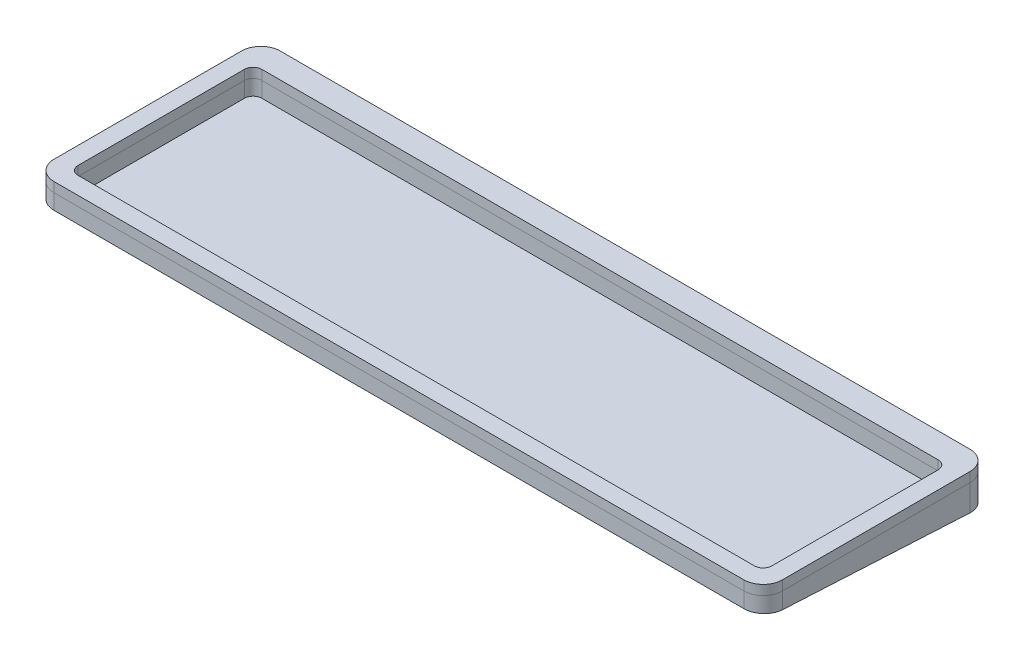
SolidWorks part; units mm, degrees
ref_plane "Front Plane" through (0, 0, 0) normal (0, 0, 1) x (1, 0, 0)
ref_plane "Top Plane" through (0, 0, 0) normal (0, 1, 0) x (1, 0, 0)
ref_plane "Right Plane" through (0, 0, 0) normal (1, 0, 0) x (0, 0, -1)
sketch "Sketch1" plane through (0, 0, 0) normal (0, 1, 0) x (1, 0, 0)
  line L0 (-179.825, 47.6224) -> (-179.825, 47.625)
  line L1 (-179.8217, 47.625) -> (179.825, 47.625)
  line L2 (-179.825, 47.6224) -> (-179.825, -47.625)
  line L3 (-179.825, -47.625) -> (179.825, -47.625)
  line L4 (179.825, 47.625) -> (179.825, -47.625)
  line L5 (-179.825, 47.625) -> (179.825, -47.625) construction
  line L6 (-179.825, -47.625) -> (179.825, 47.625) construction
  line L7 (-179.825, 47.625) -> (-179.8217, 47.625)
  circle A4 centre (157.075, 19.175) radius 1.1
  circle A5 centre (136.925, -16.775) radius 1.1
  circle A6 centre (-153.475, 33.725) radius 1.1
  circle A7 centre (17.925, 22.275) radius 1.1
  circle A8 centre (17.875, -35.075) radius 1.1
  circle A9 centre (-130.375, -35.725) radius 1.1
  point P0 (0, 0)
  point P7 (179.7842, -47.6142)
  point P8 (179.825, -47.6777)
  point P9 (179.825, 47.6224)
  point P11 (0, 0)
  point P12 (-179.8245, -47.6227)
  point P13 (179.8032, 47.6192)
  point P14 (-179.825, -47.6082)
  point P17 (-179.8242, 47.6248)
  point P30 (-179.7778, 47.6125)
  point P31 (-179.8245, 47.625)
  dimension "D4" = 2.2
  dimension "D7" = 2.2
  dimension "D8" = 2.2
  dimension "D9" = 2.2
  dimension "D10" = 2.2
  dimension "D11" = 2.2
  dimension "D1" = 359.65
  dimension "D2" = 95.25
  dimension "D5" = 22.75
  dimension "D6" = 28.45
  dimension "D12" = 42.9
  dimension "D13" = 30.85
  dimension "D14" = 25.35
  dimension "D15" = 161.9
  dimension "D16" = 12.55
  dimension "D17" = 161.95
  dimension "D18" = 11.9
  dimension "D19" = 49.45
  dimension "D20" = 13.9
  dimension "D21" = 26.35
sketch "Sketch2" plane through (0, 0, 0) normal (0, 1, 0) x (1, 0, 0)
  line L0 (-188.825, 54.625) -> (-188.825, 60.625)
  line L1 (-188.825, 60.625) -> (-182.825, 60.625)
  line L4 (-179.825, 46.625) -> (-179.825, -46.625)
  line L5 (-178.825, -47.625) -> (178.825, -47.625)
  line L6 (179.825, 46.625) -> (179.825, -46.625)
  line L7 (-178.825, 47.625) -> (178.825, 47.625)
  line L8 (-179.825, 46.625) -> (-179.825, 47.625)
  line L9 (-182.825, 60.625) -> (188.825, 60.625)
  line L10 (-188.825, 54.625) -> (-188.825, -56.625)
  line L11 (-188.825, -56.625) -> (188.825, -56.625)
  line L12 (188.825, 60.625) -> (188.825, -56.625)
  line L13 (-179.825, 47.625) -> (-178.825, 47.625)
  line L14 (-179.825, -46.625) -> (-179.825, -47.625)
  line L15 (-179.825, -47.625) -> (-178.825, -47.625)
  line L16 (178.825, -47.625) -> (179.825, -47.625)
  line L17 (179.825, -47.625) -> (179.825, -46.625)
  line L18 (178.825, 47.625) -> (179.825, 47.625)
  line L19 (179.825, 47.625) -> (179.825, 46.625)
  circle A0 centre (157.075, 19.175) radius 1.1 construction
  circle A1 centre (136.925, -16.775) radius 1.1 construction
  circle A2 centre (17.875, -35.075) radius 1.1 construction
  circle A3 centre (17.925, 22.275) radius 1.1 construction
  circle A4 centre (-153.475, 33.725) radius 1.1 construction
  circle A5 centre (-130.375, -35.725) radius 1.1 construction
  circle A10 centre (157.075, 19.175) radius 1.1
  circle A11 centre (136.925, -16.775) radius 1.1
  circle A12 centre (17.875, -35.075) radius 1.1
  circle A13 centre (17.925, 22.275) radius 1.1
  circle A14 centre (-153.475, 33.725) radius 1.1
  circle A15 centre (-130.375, -35.725) radius 1.1
  point P14 (188.825, 60.625)
  point P29 (188.825, 60.2138)
  point P30 (0, 0)
  point P32 (188.825, -56.625)
  point P33 (188.825, -56.1865)
  point P34 (-188.825, -56.625)
  point P37 (0, 0)
  dimension "D1" = 13
  dimension "D2" = 9
  dimension "D3" = 9
  dimension "D4" = 9
extrude "Boss-Extrude1" add sketch "Sketch2" along normal blind 13 contours L10 L11 L12 L9 L18 L19 L6 L17 L16 L5 L15 L14 L4 L8 L13 L7 region at (-184.8707, 0, -57.625)
sketch "Sketch4" plane through (0, 0, 0) normal (0, -1, 0) x (1, 0, 0)
  line L0 (188.825, -60.625) -> (188.825, 56.625) construction
  line L1 (-188.825, -60.625) -> (188.825, -60.625) construction
  line L2 (-188.825, -60.625) -> (-188.825, 56.625) construction
  line L3 (-188.825, 56.625) -> (188.825, 56.625) construction
  line L4 (-179.825, 47.625) -> (-179.825, -47.625)
  line L5 (179.825, 47.625) -> (-179.825, 47.625)
  line L6 (179.825, -47.625) -> (179.825, 47.625)
  line L7 (-179.825, -47.625) -> (179.825, -47.625)
  line L8 (-179.825, 47.625) -> (-179.825, -47.625)
  line L10 (179.825, -47.625) -> (179.825, 47.625)
  line L11 (-179.825, -47.625) -> (179.825, -47.625)
  line L12 (188.825, -60.625) -> (188.825, 56.625)
  line L13 (-188.825, -60.625) -> (188.825, -60.625)
  line L14 (-188.825, -60.625) -> (-188.825, 56.625)
  line L15 (-188.825, 56.625) -> (188.825, 56.625)
  line M10 (-179.825, -47.625) -> (-179.825, 47.625)
  line M12 (-179.825, 47.625) -> (179.825, 47.625)
  line M14 (179.825, 47.625) -> (179.825, -47.625)
  line M16 (179.825, -47.625) -> (-179.825, -47.625)
  line M17 (-188.825, 56.625) -> (-188.825, -60.625)
  line M19 (-188.825, -60.625) -> (188.825, -60.625)
  line M21 (188.825, -60.625) -> (188.825, 56.625)
  line M23 (188.825, 56.625) -> (-188.825, 56.625)
  dimension "D1" = 0
extrude "Boss-Extrude3" add sketch "Sketch4" along normal blind 10.5 contours M17 M19 M21 M23 M16 M10 M12 M14 | M16 M14 M12 M10 region at (0, 0, 0) region at (0, 0, -56.6707)
sketch "Sketch8" plane through (-188.825, 0, 0) normal (-1, 0, 0) x (0, 0, 1)
  line L0 (54.6255, 0) -> (-57.625, 0) construction
  line L1 (-60.625, 13) -> (-60.625, -10.5) construction
  line L4 (-60.625, -6.1008) -> (-60.625, -10.5)
  line L5 (-60.625, -10.5) -> (56.625, -10.5)
  line L11 (56.625, 0.044) -> (56.625, -10.5)
  line L13 (-60.625, -6.1008) -> (56.625, 0.044)
  point P3 (-60.625, -6.1008)
  dimension "D1" = 2
  dimension "D2" = 10.5
extrude "Cut-Extrude4" cut sketch "Sketch8" against normal blind 400
sketch "Sketch9" plane through (0, 0, 0) normal (0, 1, 0) x (1, 0, 0)
  line L0 (-121.9453, 45.1) -> (-108.9453, 45.1)
  line L1 (-121.9453, 31.1) -> (-108.9453, 31.1)
  line L2 (-122.4453, 44.6) -> (-122.4453, 31.6)
  line L3 (-108.4453, 44.6) -> (-108.4453, 31.6)
  line L4 (-102.8953, 45.1) -> (-89.8953, 45.1)
  line L5 (-102.8953, 31.1) -> (-89.8953, 31.1)
  line L6 (-103.3953, 44.6) -> (-103.3953, 31.6)
  line L7 (-89.3953, 44.6) -> (-89.3953, 31.6)
  line L8 (-83.8453, 45.1) -> (-70.8453, 45.1)
  line L9 (-83.8453, 31.1) -> (-70.8453, 31.1)
  line L10 (-84.3453, 44.6) -> (-84.3453, 31.6)
  line L11 (-70.3453, 44.6) -> (-70.3453, 31.6)
  line L12 (-64.7953, 45.1) -> (-51.7953, 45.1)
  line L13 (-64.7953, 31.1) -> (-51.7953, 31.1)
  line L14 (-65.2953, 44.6) -> (-65.2953, 31.6)
  line L15 (-51.2953, 44.6) -> (-51.2953, 31.6)
  line L16 (-45.7453, 45.1) -> (-32.7453, 45.1)
  line L17 (-45.7453, 31.1) -> (-32.7453, 31.1)
  line L18 (-46.2453, 44.6) -> (-46.2453, 31.6)
  line L19 (-32.2453, 44.6) -> (-32.2453, 31.6)
  line L20 (-26.6953, 45.1) -> (-13.6953, 45.1)
  line L21 (-26.6953, 31.1) -> (-13.6953, 31.1)
  line L22 (-27.1953, 44.6) -> (-27.1953, 31.6)
  line L23 (-13.1953, 44.6) -> (-13.1953, 31.6)
  line L24 (-7.6453, 45.1) -> (5.3547, 45.1)
  line L25 (-7.6453, 31.1) -> (5.3547, 31.1)
  line L26 (-8.1453, 44.6) -> (-8.1453, 31.6)
  line L27 (5.8547, 44.6) -> (5.8547, 31.6)
  line L28 (11.4047, 45.1) -> (24.4047, 45.1)
  line L29 (11.4047, 31.1) -> (24.4047, 31.1)
  line L30 (10.9047, 44.6) -> (10.9047, 31.6)
  line L31 (24.9047, 44.6) -> (24.9047, 31.6)
  line L32 (30.4547, 45.1) -> (43.4547, 45.1)
  line L33 (30.4547, 31.1) -> (43.4547, 31.1)
  line L34 (29.9547, 44.6) -> (29.9547, 31.6)
  line L35 (43.9547, 44.6) -> (43.9547, 31.6)
  line L36 (49.5047, 45.1) -> (62.5047, 45.1)
  line L37 (49.5047, 31.1) -> (62.5047, 31.1)
  line L38 (49.0047, 44.6) -> (49.0047, 31.6)
  line L39 (63.0047, 44.6) -> (63.0047, 31.6)
  line L40 (68.5547, 45.1) -> (81.5547, 45.1)
  line L41 (68.5547, 31.1) -> (81.5547, 31.1)
  line L42 (68.0547, 44.6) -> (68.0547, 31.6)
  line L43 (82.0547, 44.6) -> (82.0547, 31.6)
  line L44 (87.6047, 45.1) -> (100.6047, 45.1)
  line L45 (87.6047, 31.1) -> (100.6047, 31.1)
  line L46 (87.1047, 44.6) -> (87.1047, 31.6)
  line L47 (101.1047, 44.6) -> (101.1047, 31.6)
  line L48 (106.6547, 45.1) -> (119.6547, 45.1)
  line L49 (106.6547, 31.1) -> (119.6547, 31.1)
  line L50 (106.1547, 44.6) -> (106.1547, 31.6)
  line L51 (120.1547, 44.6) -> (120.1547, 31.6)
  line L52 (135.2297, 45.1) -> (148.2297, 45.1)
  line L53 (135.2297, 31.1) -> (148.2297, 31.1)
  line L54 (134.7297, 44.6) -> (134.7297, 31.6)
  line L55 (148.7297, 44.6) -> (148.7297, 31.6)
  line L56 (150.6677, 44.1) -> (156.6677, 44.1)
  line L57 (150.6677, 29.1) -> (156.6677, 29.1)
  line L58 (150.1677, 43.6) -> (150.1677, 29.6)
  line L59 (157.1677, 43.6) -> (157.1677, 29.6)
  line L60 (126.7917, 44.1) -> (132.7917, 44.1)
  line L61 (126.7917, 29.1) -> (132.7917, 29.1)
  line L62 (126.2917, 43.6) -> (126.2917, 29.6)
  line L63 (133.2917, 43.6) -> (133.2917, 29.6)
  line L64 (163.8047, 45.1) -> (176.8047, 45.1)
  line L65 (163.8047, 31.1) -> (176.8047, 31.1)
  line L66 (163.3047, 44.6) -> (163.3047, 31.6)
  line L67 (177.3047, 44.6) -> (177.3047, 31.6)
  line L68 (-117.1828, 26.05) -> (-104.1828, 26.05)
  line L69 (-117.1828, 12.05) -> (-104.1828, 12.05)
  line L70 (-117.6828, 25.55) -> (-117.6828, 12.55)
  line L71 (-103.6828, 25.55) -> (-103.6828, 12.55)
  line L72 (-93.3703, 26.05) -> (-80.3703, 26.05)
  line L73 (-93.3703, 12.05) -> (-80.3703, 12.05)
  line L74 (-93.8703, 25.55) -> (-93.8703, 12.55)
  line L75 (-79.8703, 25.55) -> (-79.8703, 12.55)
  line L76 (-74.3203, 26.05) -> (-61.3203, 26.05)
  line L77 (-74.3203, 12.05) -> (-61.3203, 12.05)
  line L78 (-74.8203, 25.55) -> (-74.8203, 12.55)
  line L79 (-60.8203, 25.55) -> (-60.8203, 12.55)
  line L80 (-55.2703, 26.05) -> (-42.2703, 26.05)
  line L81 (-55.2703, 12.05) -> (-42.2703, 12.05)
  line L82 (-55.7703, 25.55) -> (-55.7703, 12.55)
  line L83 (-41.7703, 25.55) -> (-41.7703, 12.55)
  line L84 (-36.2203, 26.05) -> (-23.2203, 26.05)
  line L85 (-36.2203, 12.05) -> (-23.2203, 12.05)
  line L86 (-36.7203, 25.55) -> (-36.7203, 12.55)
  line L87 (-22.7203, 25.55) -> (-22.7203, 12.55)
  line L88 (-17.1703, 26.05) -> (-4.1703, 26.05)
  line L89 (-17.1703, 12.05) -> (-4.1703, 12.05)
  line L90 (-17.6703, 25.55) -> (-17.6703, 12.55)
  line L91 (-3.6703, 25.55) -> (-3.6703, 12.55)
  line L92 (1.8797, 26.05) -> (14.8797, 26.05)
  line L93 (1.8797, 12.05) -> (14.8797, 12.05)
  line L94 (1.3797, 25.55) -> (1.3797, 12.55)
  line L95 (15.3797, 25.55) -> (15.3797, 12.55)
  line L96 (20.9297, 26.05) -> (33.9297, 26.05)
  line L97 (20.9297, 12.05) -> (33.9297, 12.05)
  line L98 (20.4297, 25.55) -> (20.4297, 12.55)
  line L99 (34.4297, 25.55) -> (34.4297, 12.55)
  line L100 (39.9797, 26.05) -> (52.9797, 26.05)
  line L101 (39.9797, 12.05) -> (52.9797, 12.05)
  line L102 (39.4797, 25.55) -> (39.4797, 12.55)
  line L103 (53.4797, 25.55) -> (53.4797, 12.55)
  line L104 (59.0297, 26.05) -> (72.0297, 26.05)
  line L105 (59.0297, 12.05) -> (72.0297, 12.05)
  line L106 (58.5297, 25.55) -> (58.5297, 12.55)
  line L107 (72.5297, 25.55) -> (72.5297, 12.55)
  line L108 (78.0797, 26.05) -> (91.0797, 26.05)
  line L109 (78.0797, 12.05) -> (91.0797, 12.05)
  line L110 (77.5797, 25.55) -> (77.5797, 12.55)
  line L111 (91.5797, 25.55) -> (91.5797, 12.55)
  line L112 (97.1297, 26.05) -> (110.1297, 26.05)
  line L113 (97.1297, 12.05) -> (110.1297, 12.05)
  line L114 (96.6297, 25.55) -> (96.6297, 12.55)
  line L115 (110.6297, 25.55) -> (110.6297, 12.55)
  line L116 (116.1797, 26.05) -> (129.1797, 26.05)
  line L117 (116.1797, 12.05) -> (129.1797, 12.05)
  line L118 (115.6797, 25.55) -> (115.6797, 12.55)
  line L119 (129.6797, 25.55) -> (129.6797, 12.55)
  line L120 (139.9922, 26.05) -> (152.9922, 26.05)
  line L121 (139.9922, 12.05) -> (152.9922, 12.05)
  line L122 (139.4922, 25.55) -> (139.4922, 12.55)
  line L123 (153.4922, 25.55) -> (153.4922, 12.55)
  line L124 (163.8047, 26.05) -> (176.8047, 26.05)
  line L125 (163.8047, 12.05) -> (176.8047, 12.05)
  line L126 (163.3047, 25.55) -> (163.3047, 12.55)
  line L127 (177.3047, 25.55) -> (177.3047, 12.55)
  line L128 (-114.8016, 7) -> (-101.8016, 7)
  line L129 (-114.8016, -7) -> (-101.8016, -7)
  line L130 (-115.3016, 6.5) -> (-115.3016, -6.5)
  line L131 (-101.3016, 6.5) -> (-101.3016, -6.5)
  line L132 (-88.6078, 7) -> (-75.6078, 7)
  line L133 (-88.6078, -7) -> (-75.6078, -7)
  line L134 (-89.1078, 6.5) -> (-89.1078, -6.5)
  line L135 (-75.1078, 6.5) -> (-75.1078, -6.5)
  line L136 (-69.5578, 7) -> (-56.5578, 7)
  line L137 (-69.5578, -7) -> (-56.5578, -7)
  line L138 (-70.0578, 6.5) -> (-70.0578, -6.5)
  line L139 (-56.0578, 6.5) -> (-56.0578, -6.5)
  line L140 (-50.5078, 7) -> (-37.5078, 7)
  line L141 (-50.5078, -7) -> (-37.5078, -7)
  line L142 (-51.0078, 6.5) -> (-51.0078, -6.5)
  line L143 (-37.0078, 6.5) -> (-37.0078, -6.5)
  line L144 (-31.4578, 7) -> (-18.4578, 7)
  line L145 (-31.4578, -7) -> (-18.4578, -7)
  line L146 (-31.9578, 6.5) -> (-31.9578, -6.5)
  line L147 (-17.9578, 6.5) -> (-17.9578, -6.5)
  line L148 (-12.4078, 7) -> (0.5922, 7)
  line L149 (-12.4078, -7) -> (0.5922, -7)
  line L150 (-12.9078, 6.5) -> (-12.9078, -6.5)
  line L151 (1.0922, 6.5) -> (1.0922, -6.5)
  line L152 (6.6422, 7) -> (19.6422, 7)
  line L153 (6.6422, -7) -> (19.6422, -7)
  line L154 (6.1422, 6.5) -> (6.1422, -6.5)
  line L155 (20.1422, 6.5) -> (20.1422, -6.5)
  line L156 (25.6922, 7) -> (38.6922, 7)
  line L157 (25.6922, -7) -> (38.6922, -7)
  line L158 (25.1922, 6.5) -> (25.1922, -6.5)
  line L159 (39.1922, 6.5) -> (39.1922, -6.5)
  line L160 (44.7422, 7) -> (57.7422, 7)
  line L161 (44.7422, -7) -> (57.7422, -7)
  line L162 (44.2422, 6.5) -> (44.2422, -6.5)
  line L163 (58.2422, 6.5) -> (58.2422, -6.5)
  line L164 (63.7922, 7) -> (76.7922, 7)
  line L165 (63.7922, -7) -> (76.7922, -7)
  line L166 (63.2922, 6.5) -> (63.2922, -6.5)
  line L167 (77.2922, 6.5) -> (77.2922, -6.5)
  line L168 (82.8422, 7) -> (95.8422, 7)
  line L169 (82.8422, -7) -> (95.8422, -7)
  line L170 (82.3422, 6.5) -> (82.3422, -6.5)
  line L171 (96.3422, 6.5) -> (96.3422, -6.5)
  line L172 (101.8922, 7) -> (114.8922, 7)
  line L173 (101.8922, -7) -> (114.8922, -7)
  line L174 (101.3922, 6.5) -> (101.3922, -6.5)
  line L175 (115.3922, 6.5) -> (115.3922, -6.5)
  line L176 (132.8484, 7) -> (145.8484, 7)
  line L177 (132.8484, -7) -> (145.8484, -7)
  line L178 (132.3484, 6.5) -> (132.3484, -6.5)
  line L179 (146.3484, 6.5) -> (146.3484, -6.5)
  line L180 (148.2864, 6) -> (154.2864, 6)
  line L181 (148.2864, -9) -> (154.2864, -9)
  line L182 (147.7864, 5.5) -> (147.7864, -8.5)
  line L183 (154.7864, 5.5) -> (154.7864, -8.5)
  line L184 (124.4104, 6) -> (130.4104, 6)
  line L185 (124.4104, -9) -> (130.4104, -9)
  line L186 (123.9104, 5.5) -> (123.9104, -8.5)
  line L187 (130.9104, 5.5) -> (130.9104, -8.5)
  line L188 (163.8047, 7) -> (176.8047, 7)
  line L189 (163.8047, -7) -> (176.8047, -7)
  line L190 (163.3047, 6.5) -> (163.3047, -6.5)
  line L191 (177.3047, 6.5) -> (177.3047, -6.5)
  line L192 (-110.0391, -12.05) -> (-97.0391, -12.05)
  line L193 (-110.0391, -26.05) -> (-97.0391, -26.05)
  line L194 (-110.5391, -12.55) -> (-110.5391, -25.55)
  line L195 (-96.5391, -12.55) -> (-96.5391, -25.55)
  line L196 (-94.6011, -13.05) -> (-88.6011, -13.05)
  line L197 (-94.6011, -28.05) -> (-88.6011, -28.05)
  line L198 (-95.1011, -13.55) -> (-95.1011, -27.55)
  line L199 (-88.1011, -13.55) -> (-88.1011, -27.55)
  line L200 (-118.4771, -13.05) -> (-112.4771, -13.05)
  line L201 (-118.4771, -28.05) -> (-112.4771, -28.05)
  line L202 (-118.9771, -13.55) -> (-118.9771, -27.55)
  line L203 (-111.9771, -13.55) -> (-111.9771, -27.55)
  line L204 (-79.0828, -12.05) -> (-66.0828, -12.05)
  line L205 (-79.0828, -26.05) -> (-66.0828, -26.05)
  line L206 (-79.5828, -12.55) -> (-79.5828, -25.55)
  line L207 (-65.5828, -12.55) -> (-65.5828, -25.55)
  line L208 (-60.0328, -12.05) -> (-47.0328, -12.05)
  line L209 (-60.0328, -26.05) -> (-47.0328, -26.05)
  line L210 (-60.5328, -12.55) -> (-60.5328, -25.55)
  line L211 (-46.5328, -12.55) -> (-46.5328, -25.55)
  line L212 (-40.9828, -12.05) -> (-27.9828, -12.05)
  line L213 (-40.9828, -26.05) -> (-27.9828, -26.05)
  line L214 (-41.4828, -12.55) -> (-41.4828, -25.55)
  line L215 (-27.4828, -12.55) -> (-27.4828, -25.55)
  line L216 (-21.9328, -12.05) -> (-8.9328, -12.05)
  line L217 (-21.9328, -26.05) -> (-8.9328, -26.05)
  line L218 (-22.4328, -12.55) -> (-22.4328, -25.55)
  line L219 (-8.4328, -12.55) -> (-8.4328, -25.55)
  line L220 (-2.8828, -12.05) -> (10.1172, -12.05)
  line L221 (-2.8828, -26.05) -> (10.1172, -26.05)
  line L222 (-3.3828, -12.55) -> (-3.3828, -25.55)
  line L223 (10.6172, -12.55) -> (10.6172, -25.55)
  line L224 (16.1672, -12.05) -> (29.1672, -12.05)
  line L225 (16.1672, -26.05) -> (29.1672, -26.05)
  line L226 (15.6672, -12.55) -> (15.6672, -25.55)
  line L227 (29.6672, -12.55) -> (29.6672, -25.55)
  line L228 (35.2172, -12.05) -> (48.2172, -12.05)
  line L229 (35.2172, -26.05) -> (48.2172, -26.05)
  line L230 (34.7172, -12.55) -> (34.7172, -25.55)
  line L231 (48.7172, -12.55) -> (48.7172, -25.55)
  line L232 (54.2672, -12.05) -> (67.2672, -12.05)
  line L233 (54.2672, -26.05) -> (67.2672, -26.05)
  line L234 (53.7672, -12.55) -> (53.7672, -25.55)
  line L235 (67.7672, -12.55) -> (67.7672, -25.55)
  line L236 (73.3172, -12.05) -> (86.3172, -12.05)
  line L237 (73.3172, -26.05) -> (86.3172, -26.05)
  line L238 (72.8172, -12.55) -> (72.8172, -25.55)
  line L239 (86.8172, -12.55) -> (86.8172, -25.55)
  line L240 (92.3672, -12.05) -> (105.3672, -12.05)
  line L241 (92.3672, -26.05) -> (105.3672, -26.05)
  line L242 (91.8672, -12.55) -> (91.8672, -25.55)
  line L243 (105.8672, -12.55) -> (105.8672, -25.55)
  line L244 (118.5609, -12.05) -> (131.5609, -12.05)
  line L245 (118.5609, -26.05) -> (131.5609, -26.05)
  line L246 (118.0609, -12.55) -> (118.0609, -25.55)
  line L247 (132.0609, -12.55) -> (132.0609, -25.55)
  line L248 (144.7547, -12.05) -> (157.7547, -12.05)
  line L249 (144.7547, -26.05) -> (157.7547, -26.05)
  line L250 (144.2547, -12.55) -> (144.2547, -25.55)
  line L251 (158.2547, -12.55) -> (158.2547, -25.55)
  line L252 (163.8047, -12.05) -> (176.8047, -12.05)
  line L253 (163.8047, -26.05) -> (176.8047, -26.05)
  line L254 (163.3047, -12.55) -> (163.3047, -25.55)
  line L255 (177.3047, -12.55) -> (177.3047, -25.55)
  line L256 (-119.5641, -31.1) -> (-106.5641, -31.1)
  line L257 (-119.5641, -45.1) -> (-106.5641, -45.1)
  line L258 (-120.0641, -31.6) -> (-120.0641, -44.6)
  line L259 (-106.0641, -31.6) -> (-106.0641, -44.6)
  line L260 (-95.7516, -31.1) -> (-82.7516, -31.1)
  line L261 (-95.7516, -45.1) -> (-82.7516, -45.1)
  line L262 (-96.2516, -31.6) -> (-96.2516, -44.6)
  line L263 (-82.2516, -31.6) -> (-82.2516, -44.6)
  line L264 (-71.9391, -31.1) -> (-58.9391, -31.1)
  line L265 (-71.9391, -45.1) -> (-58.9391, -45.1)
  line L266 (-72.4391, -31.6) -> (-72.4391, -44.6)
  line L267 (-58.4391, -31.6) -> (-58.4391, -44.6)
  line L268 (-0.5016, -31.1) -> (12.4984, -31.1)
  line L269 (-0.5016, -45.1) -> (12.4984, -45.1)
  line L270 (-1.0016, -31.6) -> (-1.0016, -44.6)
  line L271 (12.9984, -31.6) -> (12.9984, -44.6)
  line L272 (52.9984, -32.1) -> (58.9984, -32.1)
  line L273 (52.9984, -47.1) -> (58.9984, -47.1)
  line L274 (52.4984, -32.6) -> (52.4984, -46.6)
  line L275 (59.4984, -32.6) -> (59.4984, -46.6)
  line L276 (-47.0016, -32.1) -> (-41.0016, -32.1)
  line L277 (-47.0016, -47.1) -> (-41.0016, -47.1)
  line L278 (-47.5016, -32.6) -> (-47.5016, -46.6)
  line L279 (-40.5016, -32.6) -> (-40.5016, -46.6)
  line L280 (68.5547, -31.1) -> (81.5547, -31.1)
  line L281 (68.5547, -45.1) -> (81.5547, -45.1)
  line L282 (68.0547, -31.6) -> (68.0547, -44.6)
  line L283 (82.0547, -31.6) -> (82.0547, -44.6)
  line L284 (87.6047, -31.1) -> (100.6047, -31.1)
  line L285 (87.6047, -45.1) -> (100.6047, -45.1)
  line L286 (87.1047, -31.6) -> (87.1047, -44.6)
  line L287 (101.1047, -31.6) -> (101.1047, -44.6)
  line L288 (106.6547, -31.1) -> (119.6547, -31.1)
  line L289 (106.6547, -45.1) -> (119.6547, -45.1)
  line L290 (106.1547, -31.6) -> (106.1547, -44.6)
  line L291 (120.1547, -31.6) -> (120.1547, -44.6)
  line L292 (125.7047, -31.1) -> (138.7047, -31.1)
  line L293 (125.7047, -45.1) -> (138.7047, -45.1)
  line L294 (125.2047, -31.6) -> (125.2047, -44.6)
  line L295 (139.2047, -31.6) -> (139.2047, -44.6)
  line L296 (144.7547, -31.1) -> (157.7547, -31.1)
  line L297 (144.7547, -45.1) -> (157.7547, -45.1)
  line L298 (144.2547, -31.6) -> (144.2547, -44.6)
  line L299 (158.2547, -31.6) -> (158.2547, -44.6)
  line L300 (163.8047, -31.1) -> (176.8047, -31.1)
  line L301 (163.8047, -45.1) -> (176.8047, -45.1)
  line L302 (163.3047, -31.6) -> (163.3047, -44.6)
  line L303 (177.3047, -31.6) -> (177.3047, -44.6)
  line L304 (-122.9703, 47.625) -> (-103.2456, 47.625)
  line L305 (-122.9703, -47.625) -> (-103.2456, -47.625)
  line L306 (-124.9703, 45.625) -> (-124.9703, -45.625)
  line L307 (179.8297, 45.625) -> (179.8297, 7.5)
  line L308 (-103.2456, 53.125) -> (-103.2456, 47.625)
  line L309 (-124.9703, 47.625) -> (-103.2456, 47.625)
  line L311 (-101.2456, 55.125) -> (-90.2456, 55.125)
  line L312 (-88.2456, 47.625) -> (-88.2456, 53.125)
  line L313 (-23.2456, 53.125) -> (-23.2456, 47.625)
  line L314 (-21.2456, 55.125) -> (-10.2456, 55.125)
  line L315 (-8.2456, 47.625) -> (-8.2456, 53.125)
  line L316 (56.7544, 53.125) -> (56.7544, 47.625)
  line L317 (58.7544, 55.125) -> (69.7544, 55.125)
  line L318 (71.7544, 47.625) -> (71.7544, 53.125)
  line L319 (136.7544, 53.125) -> (136.7544, 47.625)
  line L320 (138.7544, 55.125) -> (149.7544, 55.125)
  line L321 (151.7544, 47.625) -> (151.7544, 53.125)
  line L322 (-88.2456, 47.625) -> (-23.2456, 47.625)
  line L323 (-8.2456, 47.625) -> (56.7544, 47.625)
  line L324 (71.7544, 47.625) -> (136.7544, 47.625)
  line L325 (151.7544, 47.625) -> (177.8297, 47.625)
  line L326 (-23.2456, -47.625) -> (-23.2456, -52.625)
  line L327 (-5.699, -47.625) -> (-5.699, -52.625)
  line L329 (-103.2456, -47.625) -> (-103.2456, -52.625)
  line L330 (-101.2456, -54.625) -> (-87.699, -54.625)
  line L331 (-85.699, -47.625) -> (-85.699, -52.625)
  line L332 (-21.2456, -54.625) -> (-7.699, -54.625)
  line L333 (56.7544, -47.625) -> (56.7544, -52.625)
  line L334 (74.301, -47.625) -> (74.301, -52.625)
  line L335 (58.7544, -54.625) -> (72.301, -54.625)
  line L336 (136.7544, -47.625) -> (136.7544, -52.625)
  line L337 (154.301, -47.625) -> (154.301, -52.625)
  line L338 (138.7544, -54.625) -> (152.301, -54.625)
  line L339 (-85.699, -47.625) -> (-23.2456, -47.625)
  line L340 (-5.699, -47.625) -> (56.7544, -47.625)
  line L341 (74.301, -47.625) -> (136.7544, -47.625)
  line L342 (154.301, -47.625) -> (177.8297, -47.625)
  line L343 (179.8297, -7.5) -> (179.8297, -45.625)
  line L344 (179.8297, 7.5) -> (184.9092, 7.5)
  line L346 (179.8297, -7.5) -> (184.9092, -7.5)
  line L347 (186.9092, 5.5) -> (186.9092, -5.5)
  arc A0 (-121.9453, 45.1) -> (-122.4453, 44.6) centre (-121.9453, 44.6) ccw
  arc A1 (-108.4453, 44.6) -> (-108.9453, 45.1) centre (-108.9453, 44.6) ccw
  arc A2 (-122.4453, 31.6) -> (-121.9453, 31.1) centre (-121.9453, 31.6) ccw
  arc A3 (-108.9453, 31.1) -> (-108.4453, 31.6) centre (-108.9453, 31.6) ccw
  arc A4 (-102.8953, 45.1) -> (-103.3953, 44.6) centre (-102.8953, 44.6) ccw
  arc A5 (-89.3953, 44.6) -> (-89.8953, 45.1) centre (-89.8953, 44.6) ccw
  arc A6 (-103.3953, 31.6) -> (-102.8953, 31.1) centre (-102.8953, 31.6) ccw
  arc A7 (-89.8953, 31.1) -> (-89.3953, 31.6) centre (-89.8953, 31.6) ccw
  arc A8 (-83.8453, 45.1) -> (-84.3453, 44.6) centre (-83.8453, 44.6) ccw
  arc A9 (-70.3453, 44.6) -> (-70.8453, 45.1) centre (-70.8453, 44.6) ccw
  arc A10 (-84.3453, 31.6) -> (-83.8453, 31.1) centre (-83.8453, 31.6) ccw
  arc A11 (-70.8453, 31.1) -> (-70.3453, 31.6) centre (-70.8453, 31.6) ccw
  arc A12 (-64.7953, 45.1) -> (-65.2953, 44.6) centre (-64.7953, 44.6) ccw
  arc A13 (-51.2953, 44.6) -> (-51.7953, 45.1) centre (-51.7953, 44.6) ccw
  arc A14 (-65.2953, 31.6) -> (-64.7953, 31.1) centre (-64.7953, 31.6) ccw
  arc A15 (-51.7953, 31.1) -> (-51.2953, 31.6) centre (-51.7953, 31.6) ccw
  arc A16 (-45.7453, 45.1) -> (-46.2453, 44.6) centre (-45.7453, 44.6) ccw
  arc A17 (-32.2453, 44.6) -> (-32.7453, 45.1) centre (-32.7453, 44.6) ccw
  arc A18 (-46.2453, 31.6) -> (-45.7453, 31.1) centre (-45.7453, 31.6) ccw
  arc A19 (-32.7453, 31.1) -> (-32.2453, 31.6) centre (-32.7453, 31.6) ccw
  arc A20 (-26.6953, 45.1) -> (-27.1953, 44.6) centre (-26.6953, 44.6) ccw
  arc A21 (-13.1953, 44.6) -> (-13.6953, 45.1) centre (-13.6953, 44.6) ccw
  arc A22 (-27.1953, 31.6) -> (-26.6953, 31.1) centre (-26.6953, 31.6) ccw
  arc A23 (-13.6953, 31.1) -> (-13.1953, 31.6) centre (-13.6953, 31.6) ccw
  arc A24 (-7.6453, 45.1) -> (-8.1453, 44.6) centre (-7.6453, 44.6) ccw
  arc A25 (5.8547, 44.6) -> (5.3547, 45.1) centre (5.3547, 44.6) ccw
  arc A26 (-8.1453, 31.6) -> (-7.6453, 31.1) centre (-7.6453, 31.6) ccw
  arc A27 (5.3547, 31.1) -> (5.8547, 31.6) centre (5.3547, 31.6) ccw
  arc A28 (11.4047, 45.1) -> (10.9047, 44.6) centre (11.4047, 44.6) ccw
  arc A29 (24.9047, 44.6) -> (24.4047, 45.1) centre (24.4047, 44.6) ccw
  arc A30 (10.9047, 31.6) -> (11.4047, 31.1) centre (11.4047, 31.6) ccw
  arc A31 (24.4047, 31.1) -> (24.9047, 31.6) centre (24.4047, 31.6) ccw
  arc A32 (30.4547, 45.1) -> (29.9547, 44.6) centre (30.4547, 44.6) ccw
  arc A33 (43.9547, 44.6) -> (43.4547, 45.1) centre (43.4547, 44.6) ccw
  arc A34 (29.9547, 31.6) -> (30.4547, 31.1) centre (30.4547, 31.6) ccw
  arc A35 (43.4547, 31.1) -> (43.9547, 31.6) centre (43.4547, 31.6) ccw
  arc A36 (49.5047, 45.1) -> (49.0047, 44.6) centre (49.5047, 44.6) ccw
  arc A37 (63.0047, 44.6) -> (62.5047, 45.1) centre (62.5047, 44.6) ccw
  arc A38 (49.0047, 31.6) -> (49.5047, 31.1) centre (49.5047, 31.6) ccw
  arc A39 (62.5047, 31.1) -> (63.0047, 31.6) centre (62.5047, 31.6) ccw
  arc A40 (68.5547, 45.1) -> (68.0547, 44.6) centre (68.5547, 44.6) ccw
  arc A41 (82.0547, 44.6) -> (81.5547, 45.1) centre (81.5547, 44.6) ccw
  arc A42 (68.0547, 31.6) -> (68.5547, 31.1) centre (68.5547, 31.6) ccw
  arc A43 (81.5547, 31.1) -> (82.0547, 31.6) centre (81.5547, 31.6) ccw
  arc A44 (87.6047, 45.1) -> (87.1047, 44.6) centre (87.6047, 44.6) ccw
  arc A45 (101.1047, 44.6) -> (100.6047, 45.1) centre (100.6047, 44.6) ccw
  arc A46 (87.1047, 31.6) -> (87.6047, 31.1) centre (87.6047, 31.6) ccw
  arc A47 (100.6047, 31.1) -> (101.1047, 31.6) centre (100.6047, 31.6) ccw
  arc A48 (106.6547, 45.1) -> (106.1547, 44.6) centre (106.6547, 44.6) ccw
  arc A49 (120.1547, 44.6) -> (119.6547, 45.1) centre (119.6547, 44.6) ccw
  arc A50 (106.1547, 31.6) -> (106.6547, 31.1) centre (106.6547, 31.6) ccw
  arc A51 (119.6547, 31.1) -> (120.1547, 31.6) centre (119.6547, 31.6) ccw
  arc A52 (135.2297, 45.1) -> (134.7297, 44.6) centre (135.2297, 44.6) ccw
  arc A53 (148.7297, 44.6) -> (148.2297, 45.1) centre (148.2297, 44.6) ccw
  arc A54 (134.7297, 31.6) -> (135.2297, 31.1) centre (135.2297, 31.6) ccw
  arc A55 (148.2297, 31.1) -> (148.7297, 31.6) centre (148.2297, 31.6) ccw
  arc A56 (150.6677, 44.1) -> (150.1677, 43.6) centre (150.6677, 43.6) ccw
  arc A57 (157.1677, 43.6) -> (156.6677, 44.1) centre (156.6677, 43.6) ccw
  arc A58 (150.1677, 29.6) -> (150.6677, 29.1) centre (150.6677, 29.6) ccw
  arc A59 (156.6677, 29.1) -> (157.1677, 29.6) centre (156.6677, 29.6) ccw
  arc A60 (126.7917, 44.1) -> (126.2917, 43.6) centre (126.7917, 43.6) ccw
  arc A61 (133.2917, 43.6) -> (132.7917, 44.1) centre (132.7917, 43.6) ccw
  arc A62 (126.2917, 29.6) -> (126.7917, 29.1) centre (126.7917, 29.6) ccw
  arc A63 (132.7917, 29.1) -> (133.2917, 29.6) centre (132.7917, 29.6) ccw
  arc A64 (163.8047, 45.1) -> (163.3047, 44.6) centre (163.8047, 44.6) ccw
  arc A65 (177.3047, 44.6) -> (176.8047, 45.1) centre (176.8047, 44.6) ccw
  arc A66 (163.3047, 31.6) -> (163.8047, 31.1) centre (163.8047, 31.6) ccw
  arc A67 (176.8047, 31.1) -> (177.3047, 31.6) centre (176.8047, 31.6) ccw
  arc A68 (-117.1828, 26.05) -> (-117.6828, 25.55) centre (-117.1828, 25.55) ccw
  arc A69 (-103.6828, 25.55) -> (-104.1828, 26.05) centre (-104.1828, 25.55) ccw
  arc A70 (-117.6828, 12.55) -> (-117.1828, 12.05) centre (-117.1828, 12.55) ccw
  arc A71 (-104.1828, 12.05) -> (-103.6828, 12.55) centre (-104.1828, 12.55) ccw
  arc A72 (-93.3703, 26.05) -> (-93.8703, 25.55) centre (-93.3703, 25.55) ccw
  arc A73 (-79.8703, 25.55) -> (-80.3703, 26.05) centre (-80.3703, 25.55) ccw
  arc A74 (-93.8703, 12.55) -> (-93.3703, 12.05) centre (-93.3703, 12.55) ccw
  arc A75 (-80.3703, 12.05) -> (-79.8703, 12.55) centre (-80.3703, 12.55) ccw
  arc A76 (-74.3203, 26.05) -> (-74.8203, 25.55) centre (-74.3203, 25.55) ccw
  arc A77 (-60.8203, 25.55) -> (-61.3203, 26.05) centre (-61.3203, 25.55) ccw
  arc A78 (-74.8203, 12.55) -> (-74.3203, 12.05) centre (-74.3203, 12.55) ccw
  arc A79 (-61.3203, 12.05) -> (-60.8203, 12.55) centre (-61.3203, 12.55) ccw
  arc A80 (-55.2703, 26.05) -> (-55.7703, 25.55) centre (-55.2703, 25.55) ccw
  arc A81 (-41.7703, 25.55) -> (-42.2703, 26.05) centre (-42.2703, 25.55) ccw
  arc A82 (-55.7703, 12.55) -> (-55.2703, 12.05) centre (-55.2703, 12.55) ccw
  arc A83 (-42.2703, 12.05) -> (-41.7703, 12.55) centre (-42.2703, 12.55) ccw
  arc A84 (-36.2203, 26.05) -> (-36.7203, 25.55) centre (-36.2203, 25.55) ccw
  arc A85 (-22.7203, 25.55) -> (-23.2203, 26.05) centre (-23.2203, 25.55) ccw
  arc A86 (-36.7203, 12.55) -> (-36.2203, 12.05) centre (-36.2203, 12.55) ccw
  arc A87 (-23.2203, 12.05) -> (-22.7203, 12.55) centre (-23.2203, 12.55) ccw
  arc A88 (-17.1703, 26.05) -> (-17.6703, 25.55) centre (-17.1703, 25.55) ccw
  arc A89 (-3.6703, 25.55) -> (-4.1703, 26.05) centre (-4.1703, 25.55) ccw
  arc A90 (-17.6703, 12.55) -> (-17.1703, 12.05) centre (-17.1703, 12.55) ccw
  arc A91 (-4.1703, 12.05) -> (-3.6703, 12.55) centre (-4.1703, 12.55) ccw
  arc A92 (1.8797, 26.05) -> (1.3797, 25.55) centre (1.8797, 25.55) ccw
  arc A93 (15.3797, 25.55) -> (14.8797, 26.05) centre (14.8797, 25.55) ccw
  arc A94 (1.3797, 12.55) -> (1.8797, 12.05) centre (1.8797, 12.55) ccw
  arc A95 (14.8797, 12.05) -> (15.3797, 12.55) centre (14.8797, 12.55) ccw
  arc A96 (20.9297, 26.05) -> (20.4297, 25.55) centre (20.9297, 25.55) ccw
  arc A97 (34.4297, 25.55) -> (33.9297, 26.05) centre (33.9297, 25.55) ccw
  arc A98 (20.4297, 12.55) -> (20.9297, 12.05) centre (20.9297, 12.55) ccw
  arc A99 (33.9297, 12.05) -> (34.4297, 12.55) centre (33.9297, 12.55) ccw
  arc A100 (39.9797, 26.05) -> (39.4797, 25.55) centre (39.9797, 25.55) ccw
  arc A101 (53.4797, 25.55) -> (52.9797, 26.05) centre (52.9797, 25.55) ccw
  arc A102 (39.4797, 12.55) -> (39.9797, 12.05) centre (39.9797, 12.55) ccw
  arc A103 (52.9797, 12.05) -> (53.4797, 12.55) centre (52.9797, 12.55) ccw
  arc A104 (59.0297, 26.05) -> (58.5297, 25.55) centre (59.0297, 25.55) ccw
  arc A105 (72.5297, 25.55) -> (72.0297, 26.05) centre (72.0297, 25.55) ccw
  arc A106 (58.5297, 12.55) -> (59.0297, 12.05) centre (59.0297, 12.55) ccw
  arc A107 (72.0297, 12.05) -> (72.5297, 12.55) centre (72.0297, 12.55) ccw
  arc A108 (78.0797, 26.05) -> (77.5797, 25.55) centre (78.0797, 25.55) ccw
  arc A109 (91.5797, 25.55) -> (91.0797, 26.05) centre (91.0797, 25.55) ccw
  arc A110 (77.5797, 12.55) -> (78.0797, 12.05) centre (78.0797, 12.55) ccw
  arc A111 (91.0797, 12.05) -> (91.5797, 12.55) centre (91.0797, 12.55) ccw
  arc A112 (97.1297, 26.05) -> (96.6297, 25.55) centre (97.1297, 25.55) ccw
  arc A113 (110.6297, 25.55) -> (110.1297, 26.05) centre (110.1297, 25.55) ccw
  arc A114 (96.6297, 12.55) -> (97.1297, 12.05) centre (97.1297, 12.55) ccw
  arc A115 (110.1297, 12.05) -> (110.6297, 12.55) centre (110.1297, 12.55) ccw
  arc A116 (116.1797, 26.05) -> (115.6797, 25.55) centre (116.1797, 25.55) ccw
  arc A117 (129.6797, 25.55) -> (129.1797, 26.05) centre (129.1797, 25.55) ccw
  arc A118 (115.6797, 12.55) -> (116.1797, 12.05) centre (116.1797, 12.55) ccw
  arc A119 (129.1797, 12.05) -> (129.6797, 12.55) centre (129.1797, 12.55) ccw
  arc A120 (139.9922, 26.05) -> (139.4922, 25.55) centre (139.9922, 25.55) ccw
  arc A121 (153.4922, 25.55) -> (152.9922, 26.05) centre (152.9922, 25.55) ccw
  arc A122 (139.4922, 12.55) -> (139.9922, 12.05) centre (139.9922, 12.55) ccw
  arc A123 (152.9922, 12.05) -> (153.4922, 12.55) centre (152.9922, 12.55) ccw
  arc A124 (163.8047, 26.05) -> (163.3047, 25.55) centre (163.8047, 25.55) ccw
  arc A125 (177.3047, 25.55) -> (176.8047, 26.05) centre (176.8047, 25.55) ccw
  arc A126 (163.3047, 12.55) -> (163.8047, 12.05) centre (163.8047, 12.55) ccw
  arc A127 (176.8047, 12.05) -> (177.3047, 12.55) centre (176.8047, 12.55) ccw
  arc A128 (-114.8016, 7) -> (-115.3016, 6.5) centre (-114.8016, 6.5) ccw
  arc A129 (-101.3016, 6.5) -> (-101.8016, 7) centre (-101.8016, 6.5) ccw
  arc A130 (-115.3016, -6.5) -> (-114.8016, -7) centre (-114.8016, -6.5) ccw
  arc A131 (-101.8016, -7) -> (-101.3016, -6.5) centre (-101.8016, -6.5) ccw
  arc A132 (-88.6078, 7) -> (-89.1078, 6.5) centre (-88.6078, 6.5) ccw
  arc A133 (-75.1078, 6.5) -> (-75.6078, 7) centre (-75.6078, 6.5) ccw
  arc A134 (-89.1078, -6.5) -> (-88.6078, -7) centre (-88.6078, -6.5) ccw
  arc A135 (-75.6078, -7) -> (-75.1078, -6.5) centre (-75.6078, -6.5) ccw
  arc A136 (-69.5578, 7) -> (-70.0578, 6.5) centre (-69.5578, 6.5) ccw
  arc A137 (-56.0578, 6.5) -> (-56.5578, 7) centre (-56.5578, 6.5) ccw
  arc A138 (-70.0578, -6.5) -> (-69.5578, -7) centre (-69.5578, -6.5) ccw
  arc A139 (-56.5578, -7) -> (-56.0578, -6.5) centre (-56.5578, -6.5) ccw
  arc A140 (-50.5078, 7) -> (-51.0078, 6.5) centre (-50.5078, 6.5) ccw
  arc A141 (-37.0078, 6.5) -> (-37.5078, 7) centre (-37.5078, 6.5) ccw
  arc A142 (-51.0078, -6.5) -> (-50.5078, -7) centre (-50.5078, -6.5) ccw
  arc A143 (-37.5078, -7) -> (-37.0078, -6.5) centre (-37.5078, -6.5) ccw
  arc A144 (-31.4578, 7) -> (-31.9578, 6.5) centre (-31.4578, 6.5) ccw
  arc A145 (-17.9578, 6.5) -> (-18.4578, 7) centre (-18.4578, 6.5) ccw
  arc A146 (-31.9578, -6.5) -> (-31.4578, -7) centre (-31.4578, -6.5) ccw
  arc A147 (-18.4578, -7) -> (-17.9578, -6.5) centre (-18.4578, -6.5) ccw
  arc A148 (-12.4078, 7) -> (-12.9078, 6.5) centre (-12.4078, 6.5) ccw
  arc A149 (1.0922, 6.5) -> (0.5922, 7) centre (0.5922, 6.5) ccw
  arc A150 (-12.9078, -6.5) -> (-12.4078, -7) centre (-12.4078, -6.5) ccw
  arc A151 (0.5922, -7) -> (1.0922, -6.5) centre (0.5922, -6.5) ccw
  arc A152 (6.6422, 7) -> (6.1422, 6.5) centre (6.6422, 6.5) ccw
  arc A153 (20.1422, 6.5) -> (19.6422, 7) centre (19.6422, 6.5) ccw
  arc A154 (6.1422, -6.5) -> (6.6422, -7) centre (6.6422, -6.5) ccw
  arc A155 (19.6422, -7) -> (20.1422, -6.5) centre (19.6422, -6.5) ccw
  arc A156 (25.6922, 7) -> (25.1922, 6.5) centre (25.6922, 6.5) ccw
  arc A157 (39.1922, 6.5) -> (38.6922, 7) centre (38.6922, 6.5) ccw
  arc A158 (25.1922, -6.5) -> (25.6922, -7) centre (25.6922, -6.5) ccw
  arc A159 (38.6922, -7) -> (39.1922, -6.5) centre (38.6922, -6.5) ccw
  arc A160 (44.7422, 7) -> (44.2422, 6.5) centre (44.7422, 6.5) ccw
  arc A161 (58.2422, 6.5) -> (57.7422, 7) centre (57.7422, 6.5) ccw
  arc A162 (44.2422, -6.5) -> (44.7422, -7) centre (44.7422, -6.5) ccw
  arc A163 (57.7422, -7) -> (58.2422, -6.5) centre (57.7422, -6.5) ccw
  arc A164 (63.7922, 7) -> (63.2922, 6.5) centre (63.7922, 6.5) ccw
  arc A165 (77.2922, 6.5) -> (76.7922, 7) centre (76.7922, 6.5) ccw
  arc A166 (63.2922, -6.5) -> (63.7922, -7) centre (63.7922, -6.5) ccw
  arc A167 (76.7922, -7) -> (77.2922, -6.5) centre (76.7922, -6.5) ccw
  arc A168 (82.8422, 7) -> (82.3422, 6.5) centre (82.8422, 6.5) ccw
  arc A169 (96.3422, 6.5) -> (95.8422, 7) centre (95.8422, 6.5) ccw
  arc A170 (82.3422, -6.5) -> (82.8422, -7) centre (82.8422, -6.5) ccw
  arc A171 (95.8422, -7) -> (96.3422, -6.5) centre (95.8422, -6.5) ccw
  arc A172 (101.8922, 7) -> (101.3922, 6.5) centre (101.8922, 6.5) ccw
  arc A173 (115.3922, 6.5) -> (114.8922, 7) centre (114.8922, 6.5) ccw
  arc A174 (101.3922, -6.5) -> (101.8922, -7) centre (101.8922, -6.5) ccw
  arc A175 (114.8922, -7) -> (115.3922, -6.5) centre (114.8922, -6.5) ccw
  arc A176 (132.8484, 7) -> (132.3484, 6.5) centre (132.8484, 6.5) ccw
  arc A177 (146.3484, 6.5) -> (145.8484, 7) centre (145.8484, 6.5) ccw
  arc A178 (132.3484, -6.5) -> (132.8484, -7) centre (132.8484, -6.5) ccw
  arc A179 (145.8484, -7) -> (146.3484, -6.5) centre (145.8484, -6.5) ccw
  arc A180 (148.2864, 6) -> (147.7864, 5.5) centre (148.2864, 5.5) ccw
  arc A181 (154.7864, 5.5) -> (154.2864, 6) centre (154.2864, 5.5) ccw
  arc A182 (147.7864, -8.5) -> (148.2864, -9) centre (148.2864, -8.5) ccw
  arc A183 (154.2864, -9) -> (154.7864, -8.5) centre (154.2864, -8.5) ccw
  arc A184 (124.4104, 6) -> (123.9104, 5.5) centre (124.4104, 5.5) ccw
  arc A185 (130.9104, 5.5) -> (130.4104, 6) centre (130.4104, 5.5) ccw
  arc A186 (123.9104, -8.5) -> (124.4104, -9) centre (124.4104, -8.5) ccw
  arc A187 (130.4104, -9) -> (130.9104, -8.5) centre (130.4104, -8.5) ccw
  arc A188 (163.8047, 7) -> (163.3047, 6.5) centre (163.8047, 6.5) ccw
  arc A189 (177.3047, 6.5) -> (176.8047, 7) centre (176.8047, 6.5) ccw
  arc A190 (163.3047, -6.5) -> (163.8047, -7) centre (163.8047, -6.5) ccw
  arc A191 (176.8047, -7) -> (177.3047, -6.5) centre (176.8047, -6.5) ccw
  arc A192 (-110.0391, -12.05) -> (-110.5391, -12.55) centre (-110.0391, -12.55) ccw
  arc A193 (-96.5391, -12.55) -> (-97.0391, -12.05) centre (-97.0391, -12.55) ccw
  arc A194 (-110.5391, -25.55) -> (-110.0391, -26.05) centre (-110.0391, -25.55) ccw
  arc A195 (-97.0391, -26.05) -> (-96.5391, -25.55) centre (-97.0391, -25.55) ccw
  arc A196 (-94.6011, -13.05) -> (-95.1011, -13.55) centre (-94.6011, -13.55) ccw
  arc A197 (-88.1011, -13.55) -> (-88.6011, -13.05) centre (-88.6011, -13.55) ccw
  arc A198 (-95.1011, -27.55) -> (-94.6011, -28.05) centre (-94.6011, -27.55) ccw
  arc A199 (-88.6011, -28.05) -> (-88.1011, -27.55) centre (-88.6011, -27.55) ccw
  arc A200 (-118.4771, -13.05) -> (-118.9771, -13.55) centre (-118.4771, -13.55) ccw
  arc A201 (-111.9771, -13.55) -> (-112.4771, -13.05) centre (-112.4771, -13.55) ccw
  arc A202 (-118.9771, -27.55) -> (-118.4771, -28.05) centre (-118.4771, -27.55) ccw
  arc A203 (-112.4771, -28.05) -> (-111.9771, -27.55) centre (-112.4771, -27.55) ccw
  arc A204 (-79.0828, -12.05) -> (-79.5828, -12.55) centre (-79.0828, -12.55) ccw
  arc A205 (-65.5828, -12.55) -> (-66.0828, -12.05) centre (-66.0828, -12.55) ccw
  arc A206 (-79.5828, -25.55) -> (-79.0828, -26.05) centre (-79.0828, -25.55) ccw
  arc A207 (-66.0828, -26.05) -> (-65.5828, -25.55) centre (-66.0828, -25.55) ccw
  arc A208 (-60.0328, -12.05) -> (-60.5328, -12.55) centre (-60.0328, -12.55) ccw
  arc A209 (-46.5328, -12.55) -> (-47.0328, -12.05) centre (-47.0328, -12.55) ccw
  arc A210 (-60.5328, -25.55) -> (-60.0328, -26.05) centre (-60.0328, -25.55) ccw
  arc A211 (-47.0328, -26.05) -> (-46.5328, -25.55) centre (-47.0328, -25.55) ccw
  arc A212 (-40.9828, -12.05) -> (-41.4828, -12.55) centre (-40.9828, -12.55) ccw
  arc A213 (-27.4828, -12.55) -> (-27.9828, -12.05) centre (-27.9828, -12.55) ccw
  arc A214 (-41.4828, -25.55) -> (-40.9828, -26.05) centre (-40.9828, -25.55) ccw
  arc A215 (-27.9828, -26.05) -> (-27.4828, -25.55) centre (-27.9828, -25.55) ccw
  arc A216 (-21.9328, -12.05) -> (-22.4328, -12.55) centre (-21.9328, -12.55) ccw
  arc A217 (-8.4328, -12.55) -> (-8.9328, -12.05) centre (-8.9328, -12.55) ccw
  arc A218 (-22.4328, -25.55) -> (-21.9328, -26.05) centre (-21.9328, -25.55) ccw
  arc A219 (-8.9328, -26.05) -> (-8.4328, -25.55) centre (-8.9328, -25.55) ccw
  arc A220 (-2.8828, -12.05) -> (-3.3828, -12.55) centre (-2.8828, -12.55) ccw
  arc A221 (10.6172, -12.55) -> (10.1172, -12.05) centre (10.1172, -12.55) ccw
  arc A222 (-3.3828, -25.55) -> (-2.8828, -26.05) centre (-2.8828, -25.55) ccw
  arc A223 (10.1172, -26.05) -> (10.6172, -25.55) centre (10.1172, -25.55) ccw
  arc A224 (16.1672, -12.05) -> (15.6672, -12.55) centre (16.1672, -12.55) ccw
  arc A225 (29.6672, -12.55) -> (29.1672, -12.05) centre (29.1672, -12.55) ccw
  arc A226 (15.6672, -25.55) -> (16.1672, -26.05) centre (16.1672, -25.55) ccw
  arc A227 (29.1672, -26.05) -> (29.6672, -25.55) centre (29.1672, -25.55) ccw
  arc A228 (35.2172, -12.05) -> (34.7172, -12.55) centre (35.2172, -12.55) ccw
  arc A229 (48.7172, -12.55) -> (48.2172, -12.05) centre (48.2172, -12.55) ccw
  arc A230 (34.7172, -25.55) -> (35.2172, -26.05) centre (35.2172, -25.55) ccw
  arc A231 (48.2172, -26.05) -> (48.7172, -25.55) centre (48.2172, -25.55) ccw
  arc A232 (54.2672, -12.05) -> (53.7672, -12.55) centre (54.2672, -12.55) ccw
  arc A233 (67.7672, -12.55) -> (67.2672, -12.05) centre (67.2672, -12.55) ccw
  arc A234 (53.7672, -25.55) -> (54.2672, -26.05) centre (54.2672, -25.55) ccw
  arc A235 (67.2672, -26.05) -> (67.7672, -25.55) centre (67.2672, -25.55) ccw
  arc A236 (73.3172, -12.05) -> (72.8172, -12.55) centre (73.3172, -12.55) ccw
  arc A237 (86.8172, -12.55) -> (86.3172, -12.05) centre (86.3172, -12.55) ccw
  arc A238 (72.8172, -25.55) -> (73.3172, -26.05) centre (73.3172, -25.55) ccw
  arc A239 (86.3172, -26.05) -> (86.8172, -25.55) centre (86.3172, -25.55) ccw
  arc A240 (92.3672, -12.05) -> (91.8672, -12.55) centre (92.3672, -12.55) ccw
  arc A241 (105.8672, -12.55) -> (105.3672, -12.05) centre (105.3672, -12.55) ccw
  arc A242 (91.8672, -25.55) -> (92.3672, -26.05) centre (92.3672, -25.55) ccw
  arc A243 (105.3672, -26.05) -> (105.8672, -25.55) centre (105.3672, -25.55) ccw
  arc A244 (118.5609, -12.05) -> (118.0609, -12.55) centre (118.5609, -12.55) ccw
  arc A245 (132.0609, -12.55) -> (131.5609, -12.05) centre (131.5609, -12.55) ccw
  arc A246 (118.0609, -25.55) -> (118.5609, -26.05) centre (118.5609, -25.55) ccw
  arc A247 (131.5609, -26.05) -> (132.0609, -25.55) centre (131.5609, -25.55) ccw
  arc A248 (144.7547, -12.05) -> (144.2547, -12.55) centre (144.7547, -12.55) ccw
  arc A249 (158.2547, -12.55) -> (157.7547, -12.05) centre (157.7547, -12.55) ccw
  arc A250 (144.2547, -25.55) -> (144.7547, -26.05) centre (144.7547, -25.55) ccw
  arc A251 (157.7547, -26.05) -> (158.2547, -25.55) centre (157.7547, -25.55) ccw
  arc A252 (163.8047, -12.05) -> (163.3047, -12.55) centre (163.8047, -12.55) ccw
  arc A253 (177.3047, -12.55) -> (176.8047, -12.05) centre (176.8047, -12.55) ccw
  arc A254 (163.3047, -25.55) -> (163.8047, -26.05) centre (163.8047, -25.55) ccw
  arc A255 (176.8047, -26.05) -> (177.3047, -25.55) centre (176.8047, -25.55) ccw
  arc A256 (-119.5641, -31.1) -> (-120.0641, -31.6) centre (-119.5641, -31.6) ccw
  arc A257 (-106.0641, -31.6) -> (-106.5641, -31.1) centre (-106.5641, -31.6) ccw
  arc A258 (-120.0641, -44.6) -> (-119.5641, -45.1) centre (-119.5641, -44.6) ccw
  arc A259 (-106.5641, -45.1) -> (-106.0641, -44.6) centre (-106.5641, -44.6) ccw
  arc A260 (-95.7516, -31.1) -> (-96.2516, -31.6) centre (-95.7516, -31.6) ccw
  arc A261 (-82.2516, -31.6) -> (-82.7516, -31.1) centre (-82.7516, -31.6) ccw
  arc A262 (-96.2516, -44.6) -> (-95.7516, -45.1) centre (-95.7516, -44.6) ccw
  arc A263 (-82.7516, -45.1) -> (-82.2516, -44.6) centre (-82.7516, -44.6) ccw
  arc A264 (-71.9391, -31.1) -> (-72.4391, -31.6) centre (-71.9391, -31.6) ccw
  arc A265 (-58.4391, -31.6) -> (-58.9391, -31.1) centre (-58.9391, -31.6) ccw
  arc A266 (-72.4391, -44.6) -> (-71.9391, -45.1) centre (-71.9391, -44.6) ccw
  arc A267 (-58.9391, -45.1) -> (-58.4391, -44.6) centre (-58.9391, -44.6) ccw
  arc A268 (-0.5016, -31.1) -> (-1.0016, -31.6) centre (-0.5016, -31.6) ccw
  arc A269 (12.9984, -31.6) -> (12.4984, -31.1) centre (12.4984, -31.6) ccw
  arc A270 (-1.0016, -44.6) -> (-0.5016, -45.1) centre (-0.5016, -44.6) ccw
  arc A271 (12.4984, -45.1) -> (12.9984, -44.6) centre (12.4984, -44.6) ccw
  arc A272 (52.9984, -32.1) -> (52.4984, -32.6) centre (52.9984, -32.6) ccw
  arc A273 (59.4984, -32.6) -> (58.9984, -32.1) centre (58.9984, -32.6) ccw
  arc A274 (52.4984, -46.6) -> (52.9984, -47.1) centre (52.9984, -46.6) ccw
  arc A275 (58.9984, -47.1) -> (59.4984, -46.6) centre (58.9984, -46.6) ccw
  arc A276 (-47.0016, -32.1) -> (-47.5016, -32.6) centre (-47.0016, -32.6) ccw
  arc A277 (-40.5016, -32.6) -> (-41.0016, -32.1) centre (-41.0016, -32.6) ccw
  arc A278 (-47.5016, -46.6) -> (-47.0016, -47.1) centre (-47.0016, -46.6) ccw
  arc A279 (-41.0016, -47.1) -> (-40.5016, -46.6) centre (-41.0016, -46.6) ccw
  arc A280 (68.5547, -31.1) -> (68.0547, -31.6) centre (68.5547, -31.6) ccw
  arc A281 (82.0547, -31.6) -> (81.5547, -31.1) centre (81.5547, -31.6) ccw
  arc A282 (68.0547, -44.6) -> (68.5547, -45.1) centre (68.5547, -44.6) ccw
  arc A283 (81.5547, -45.1) -> (82.0547, -44.6) centre (81.5547, -44.6) ccw
  arc A284 (87.6047, -31.1) -> (87.1047, -31.6) centre (87.6047, -31.6) ccw
  arc A285 (101.1047, -31.6) -> (100.6047, -31.1) centre (100.6047, -31.6) ccw
  arc A286 (87.1047, -44.6) -> (87.6047, -45.1) centre (87.6047, -44.6) ccw
  arc A287 (100.6047, -45.1) -> (101.1047, -44.6) centre (100.6047, -44.6) ccw
  arc A288 (106.6547, -31.1) -> (106.1547, -31.6) centre (106.6547, -31.6) ccw
  arc A289 (120.1547, -31.6) -> (119.6547, -31.1) centre (119.6547, -31.6) ccw
  arc A290 (106.1547, -44.6) -> (106.6547, -45.1) centre (106.6547, -44.6) ccw
  arc A291 (119.6547, -45.1) -> (120.1547, -44.6) centre (119.6547, -44.6) ccw
  arc A292 (125.7047, -31.1) -> (125.2047, -31.6) centre (125.7047, -31.6) ccw
  arc A293 (139.2047, -31.6) -> (138.7047, -31.1) centre (138.7047, -31.6) ccw
  arc A294 (125.2047, -44.6) -> (125.7047, -45.1) centre (125.7047, -44.6) ccw
  arc A295 (138.7047, -45.1) -> (139.2047, -44.6) centre (138.7047, -44.6) ccw
  arc A296 (144.7547, -31.1) -> (144.2547, -31.6) centre (144.7547, -31.6) ccw
  arc A297 (158.2547, -31.6) -> (157.7547, -31.1) centre (157.7547, -31.6) ccw
  arc A298 (144.2547, -44.6) -> (144.7547, -45.1) centre (144.7547, -44.6) ccw
  arc A299 (157.7547, -45.1) -> (158.2547, -44.6) centre (157.7547, -44.6) ccw
  arc A300 (163.8047, -31.1) -> (163.3047, -31.6) centre (163.8047, -31.6) ccw
  arc A301 (177.3047, -31.6) -> (176.8047, -31.1) centre (176.8047, -31.6) ccw
  arc A302 (163.3047, -44.6) -> (163.8047, -45.1) centre (163.8047, -44.6) ccw
  arc A303 (176.8047, -45.1) -> (177.3047, -44.6) centre (176.8047, -44.6) ccw
  circle A306 centre (-95.7456, 51.125) radius 1
  arc A307 (-90.2456, 55.125) -> (-88.2456, 53.125) centre (-90.2456, 53.125) cw
  arc A308 (-103.2456, 53.125) -> (-101.2456, 55.125) centre (-101.2456, 53.125) cw
  arc A309 (-23.2456, 53.125) -> (-21.2456, 55.125) centre (-21.2456, 53.125) cw
  circle A310 centre (-15.7456, 51.125) radius 1
  arc A311 (-10.2456, 55.125) -> (-8.2456, 53.125) centre (-10.2456, 53.125) cw
  arc A312 (56.7544, 53.125) -> (58.7544, 55.125) centre (58.7544, 53.125) cw
  circle A313 centre (64.2544, 51.125) radius 1
  arc A314 (69.7544, 55.125) -> (71.7544, 53.125) centre (69.7544, 53.125) cw
  arc A315 (136.7544, 53.125) -> (138.7544, 55.125) centre (138.7544, 53.125) cw
  circle A316 centre (144.2544, 51.125) radius 1
  arc A317 (149.7544, 55.125) -> (151.7544, 53.125) centre (149.7544, 53.125) cw
  arc A318 (-87.699, -54.625) -> (-85.699, -52.625) centre (-87.699, -52.625) ccw
  arc A319 (-103.2456, -52.625) -> (-101.2456, -54.625) centre (-101.2456, -52.625) ccw
  circle A320 centre (-94.4723, -50.125) radius 1
  arc A321 (-23.2456, -52.625) -> (-21.2456, -54.625) centre (-21.2456, -52.625) ccw
  arc A322 (-7.699, -54.625) -> (-5.699, -52.625) centre (-7.699, -52.625) ccw
  circle A323 centre (-14.4723, -50.125) radius 1
  arc A324 (56.7544, -52.625) -> (58.7544, -54.625) centre (58.7544, -52.625) ccw
  arc A325 (72.301, -54.625) -> (74.301, -52.625) centre (72.301, -52.625) ccw
  circle A326 centre (65.5277, -50.125) radius 1
  arc A327 (136.7544, -52.625) -> (138.7544, -54.625) centre (138.7544, -52.625) ccw
  arc A328 (152.301, -54.625) -> (154.301, -52.625) centre (152.301, -52.625) ccw
  circle A329 centre (145.5277, -50.125) radius 1
  arc A330 (177.8297, -47.625) -> (179.8297, -45.625) centre (177.8297, -45.625) ccw
  arc A331 (177.8297, 47.625) -> (179.8297, 45.625) centre (177.8297, 45.625) cw
  arc A332 (-122.9703, -47.625) -> (-124.9703, -45.625) centre (-122.9703, -45.625) cw
  arc A333 (-122.9703, 47.625) -> (-124.9703, 45.625) centre (-122.9703, 45.625) ccw
  arc A334 (184.9092, -7.5) -> (186.9092, -5.5) centre (184.9092, -5.5) ccw
  arc A335 (184.9092, 7.5) -> (186.9092, 5.5) centre (184.9092, 5.5) cw
  circle A336 centre (183.1092, 0) radius 1
  point P924 (-88.2456, 55.125)
  point P927 (-103.2456, 55.125)
  point P964 (-85.699, -54.625)
  point P967 (-103.2456, -54.625)
  point P968 (24.2544, 47.625)
  point P1017 (186.9092, -7.5)
  point P1020 (186.9092, 7.5)
  dimension "D5" = 7.5
  dimension "D3" = 4
  dimension "D4" = 2
  dimension "D6" = 2
  dimension "D8" = 17.5466
  dimension "D10" = 2
  dimension "D11" = 2
  dimension "D13" = 4
  dimension "D14" = 2
  dimension "D17" = 2
  dimension "D18" = 2
  dimension "D1" = 7.5
  dimension "D2" = 15
  dimension "D9" = 7
  dimension "D12" = 2.5
  dimension "D16" = 15
  dimension "D19" = 3.8
  dimension "D7" = 4
ref_plane "Plane1" through (0, 8, 0) normal (0, 1, 0) x (1, 0, 0)
fillet "Fillet1" radius 10 4 edges at (188.825, 6.522, 56.625) (-188.825, 6.522, 56.625) (188.825, 3.4496, -60.625) (-188.825, 3.4496, -60.625)
fillet "Fillet2" radius 4.5 4 edges at (179.825, 6.5, 47.625) (-179.825, 6.5, 47.625) (179.825, 6.5, -47.625) (-179.825, 6.5, -47.625)
split "Split1" trim tools "Plane1" bodies to split 116 resulting bodies 118 119
sketch "Sketch10" plane through (0, 8, 0) normal (0, 1, 0) x (1, 0, 0)
  line L0 (-175.325, 47.625) -> (175.325, 47.625) construction
  line L1 (-180.825, 48.625) -> (180.825, 48.625)
  line L2 (-180.825, 48.625) -> (-180.825, -48.625)
  line L3 (-180.825, -48.625) -> (180.825, -48.625)
  line L4 (180.825, 48.625) -> (180.825, -48.625)
  line L5 (-179.825, 43.125) -> (-179.825, -43.125) construction
  line L6 (179.825, 43.125) -> (179.825, -43.125) construction
  line L7 (-175.325, -47.625) -> (175.325, -47.625) construction
  dimension "D1" = 1
  dimension "D2" = 1
  dimension "D3" = 1
  dimension "D4" = 1
